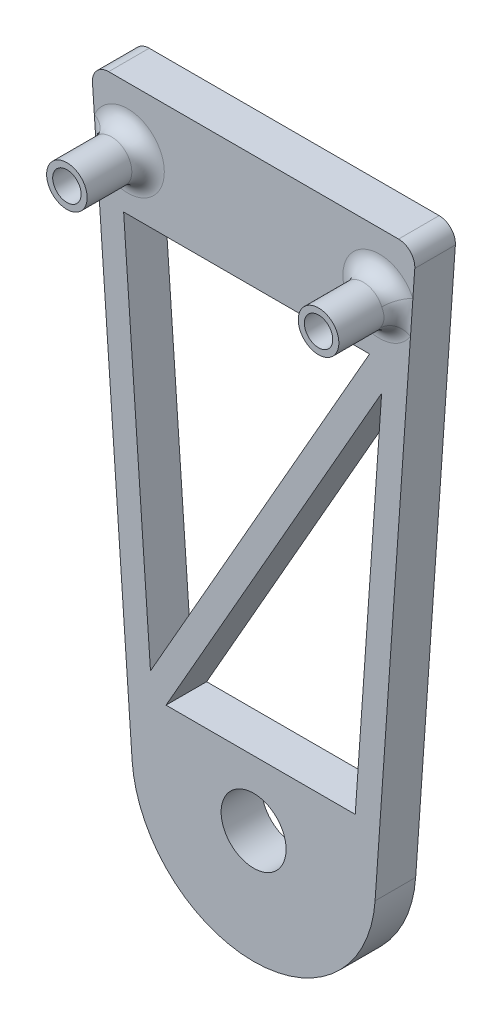
SolidWorks part; units mm, degrees
ref_plane "Alzado" through (0, 0, 0) normal (0, 0, 1) x (1, 0, 0)
ref_plane "Planta" through (0, 0, 0) normal (0, 1, 0) x (1, 0, 0)
ref_plane "Vista lateral" through (0, 0, 0) normal (1, 0, 0) x (0, 0, -1)
sketch "Croquis1" plane through (0, 0, 0) normal (0, 0, 1) x (1, 0, 0)
  line L0 (0, 0) -> (0, -128.0927) construction
  line L1 (-20.0014, 0) -> (20.0014, 0)
  line L2 (20.0014, 0) -> (14.9635, -72.0463)
  line L3 (-20.0014, 0) -> (-14.9635, -72.0463)
  line L4 (-16.0119, -14.0463) -> (16.0119, -14.0463)
  line L5 (16.0119, -14.0463) -> (12.5155, -64.0463)
  line L6 (12.5155, -64.0463) -> (-12.5155, -64.0463)
  line L7 (-12.5155, -64.0463) -> (-16.0119, -14.0463)
  line L8 (-14.9635, -72.0463) -> (14.9635, -72.0463) construction
  line L9 (-12.7041, -61.35) -> (14.2849, -14.0463)
  line L10 (-12.5155, -64.0463) -> (16.0119, -14.0463) construction
  line L11 (-10.7886, -64.0463) -> (15.7707, -17.496)
  arc A0 (14.9635, -72.0463) -> (-14.9635, -72.0463) centre (0, -71) cw
  circle A1 centre (-15.5, -7.2763) radius 2.5
  circle A2 centre (15.5, -7.2763) radius 2.5
  circle A3 centre (-15.5, -7.2763) radius 1.75
  circle A4 centre (15.5, -7.2763) radius 1.75
  circle A5 centre (0, -72.0463) radius 4
  point P12 (0, -86)
  point P19 (0, -64.0463)
  dimension "D1" = 15
  dimension "D4" = 64.77
  dimension "D5" = 5
  dimension "D7" = 3.5
  dimension "D10" = 8
  dimension "D2" = 86
  dimension "D3" = 86
  dimension "D6" = 31
  dimension "D8" = 3
  dimension "D9" = 50
  dimension "D11" = 8
  dimension "D12" = 3
extrude "Saliente-Extruir1" add sketch "Croquis1" along normal mid plane 5 contours L0 L1 L3 A0 A1 | A1 | A2 | L1 L0 A0 L2 A2 | L6 L11 L5 L4 L9 L7 region at (0, -0.9485, 0) region at (1.6928, -39.1355, 0) region at (-17.9293, -7.2763, 0) region at (13.0707, -7.2763, 0)
extrude "Saliente-Extruir2" add sketch "Croquis1<3>" along normal blind 10 contours A1 | A2 | A3 | A4
sketch "Croquis1<3>" plane through (0, 0, 0) normal (0, 0, 1) x (1, 0, 0) same geometry as "Croquis1"
fillet "Redondeo1" radius 2 2 edges at (18, -7.2763, 2.5) (-13, -7.2763, 2.5)
fillet "Redondeo2" radius 2 2 edges at (20.0014, 0, 0) (-20.0014, 0, 0)
